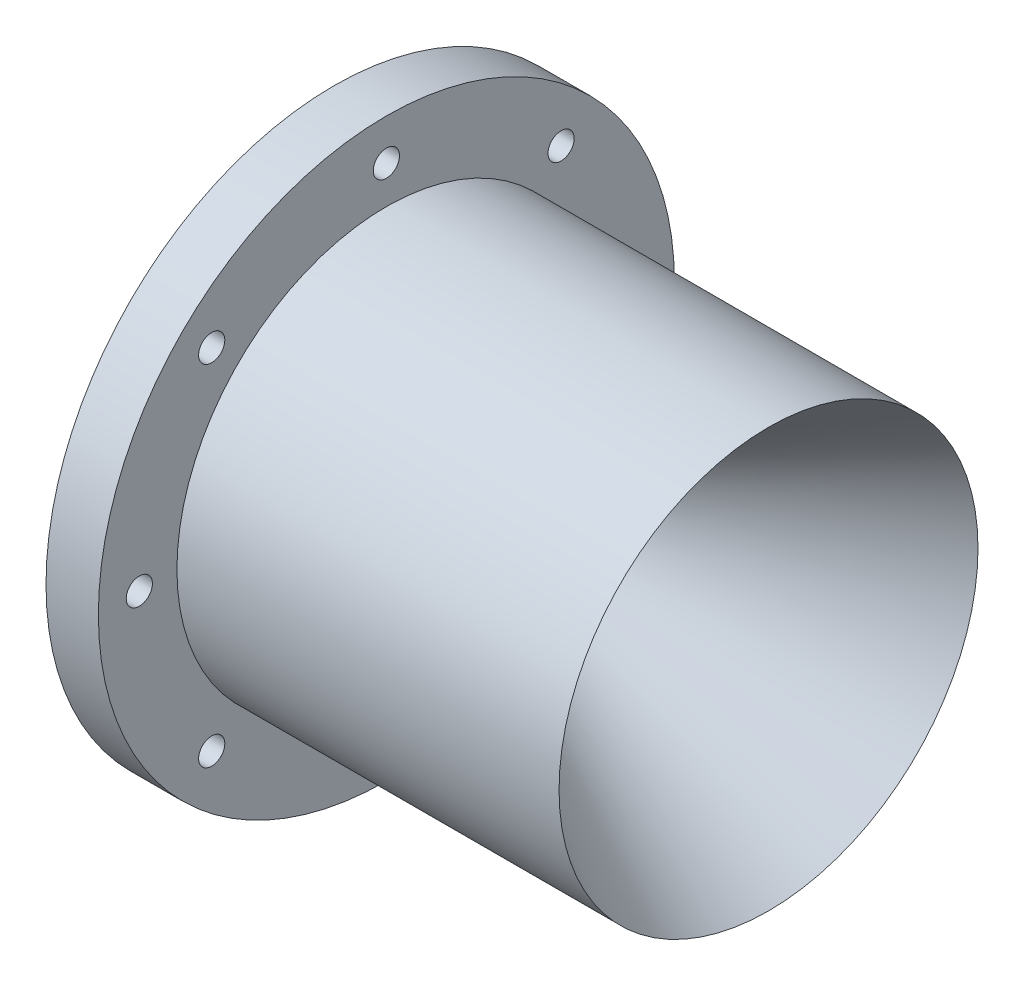
SolidWorks part; units mm, degrees
material "C (Graphite)"
ref_plane "Front Plane" through (0, 0, 0) normal (0, 0, 1) x (1, 0, 0)
ref_plane "Top Plane" through (0, 0, 0) normal (0, 1, 0) x (1, 0, 0)
ref_plane "Right Plane" through (0, 0, 0) normal (1, 0, 0) x (0, 0, -1)
sketch "Sketch1" plane through (0, 0, 0) normal (0, 0, 1) x (1, 0, 0)
  line L0 (0, 0) -> (215.3765, 0) construction
  line L1 (0, 0) -> (0, 93.6004) construction
  line L3 (0, 7.9375) -> (72.3242, 50.8)
  line L10 (0, 7.9375) -> (-12.7, 7.9375)
  line L22 (-12.7, 7.9375) -> (-33.0473, 41.275)
  line L23 (-33.0473, 50.8) -> (-33.0473, 41.275)
  line L24 (-33.0473, 50.8) -> (-33.0473, 69.85)
  line L25 (-33.0473, 69.85) -> (-20.3473, 69.85)
  line L26 (-20.3473, 69.85) -> (-20.3473, 50.8)
  line L27 (-20.3473, 50.8) -> (72.3242, 50.8)
  point P3 (0, 0)
  point P5 (0, 0)
  point P10 (0, 0)
  point P14 (0, 0)
  dimension "D3" = 7.9375
  dimension "D4" = 9.525
  dimension "D7" = 12.7
  dimension "D10" = 50.8
  dimension "D11" = 19.05
  dimension "D12" = 12.7
revolve "Revolve1" add sketch "Sketch1" angle 360 about L0
sketch "Sketch2" plane through (-33.0473, 0, 0) normal (-1, 0, 0) x (0, 0, 1)
  circle A0 centre (0, 0) radius 47.625
  circle A1 centre (0, 0) radius 49.53
  dimension "D1" = 99.06
  dimension "D2" = 95.25
extrude "Cut-Extrude1" cut sketch "Sketch2" against normal blind 1.1176
sketch "Sketch3" plane through (-33.0473, 0, 0) normal (-1, 0, 0) x (0, 0, 1)
  circle A0 centre (0, 59.9186) radius 3.175
  circle A1 centre (42.3688, 42.3688) radius 3.175
  circle A2 centre (59.9186, 0) radius 3.175
  circle A3 centre (42.3688, -42.3688) radius 3.175
  circle A4 centre (0, -59.9186) radius 3.175
  circle A5 centre (-42.3688, -42.3688) radius 3.175
  circle A6 centre (-59.9186, 0) radius 3.175
  circle A7 centre (-42.3688, 42.3688) radius 3.175
  point P36 (0, 0)
  dimension "D1" = 6.35
  dimension "D2" = 59.9186
  dimension "D3" = 8
extrude "Cut-Extrude2" cut sketch "Sketch3" against normal up to next
